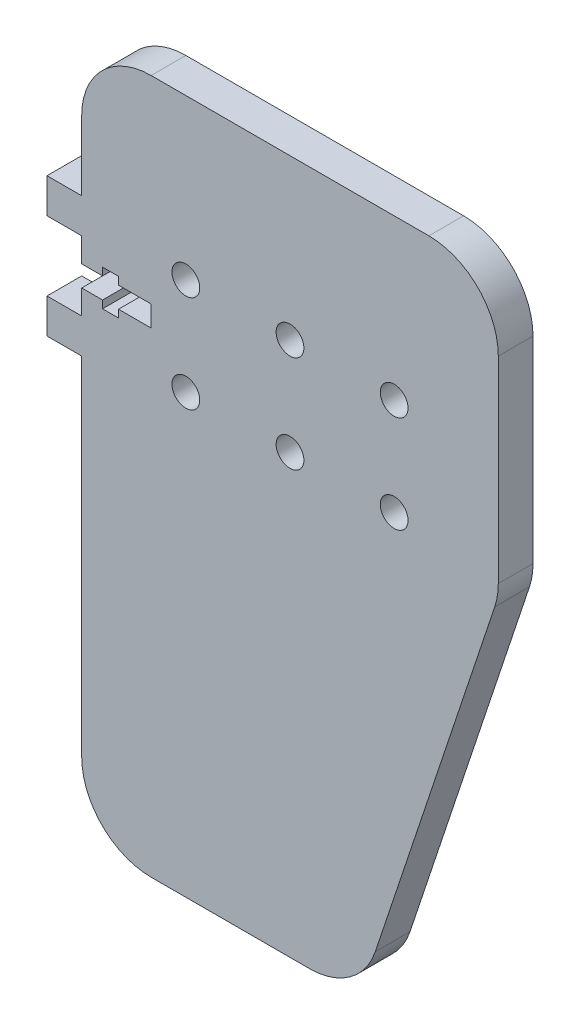
SolidWorks part; units mm, degrees
ref_plane "Plan de face" through (0, 0, 0) normal (0, 0, 1) x (1, 0, 0)
ref_plane "Plan de dessus" through (0, 0, 0) normal (0, 1, 0) x (1, 0, 0)
ref_plane "Plan de droite" through (0, 0, 0) normal (1, 0, 0) x (0, 0, -1)
sketch "Esquisse1" plane through (0, 0, 0) normal (0, 0, 1) x (1, 0, 0)
  line L0 (0, 391.1056) -> (0, -367.5965) construction
  line L1 (0, 0) -> (440.261, 0) construction
  line L2 (0, 80) -> (0, 100)
  line L3 (0, 100) -> (60, 100)
  line L4 (60, 100) -> (60, 60)
  line L5 (60, 60) -> (40, 0)
  line L6 (0, 0) -> (40, 0)
  line L8 (0, 0) -> (0, 60)
  line L9 (15, 77) -> (45, 77) construction
  circle A0 centre (15, 77) radius 2
  circle A1 centre (30, 77) radius 2
  circle A2 centre (45, 77) radius 2
  circle A3 centre (45, 63) radius 2
  circle A4 centre (30, 63) radius 2
  circle A5 centre (15, 63) radius 2
  line B0 (3, 72.6) -> (5.3, 72.6)
  line B1 (5.3, 68.5) -> (10, 68.5)
  line B2 (10, 71.5) -> (5.3, 71.5)
  line B3 (5.3, 72.6) -> (5.3, 71.5)
  line B4 (0, 70) -> (11.2208, 70) construction
  line B5 (0, 71.5) -> (0, 75)
  line B6 (-5, 75) -> (-5, 80)
  line B7 (-5, 80) -> (0, 80)
  line B8 (-5, 75) -> (0, 75)
  line B9 (0, 68.5) -> (0, 65)
  line B10 (0, 65) -> (-5, 65)
  line B11 (-5, 65) -> (-5, 60)
  line B12 (-5, 60) -> (0, 60)
  line B13 (0, 71.5) -> (0, 68.5) construction
  line B14 (0, 68.5) -> (3, 68.5)
  line B15 (5.3, 68.5) -> (5.3, 67.4)
  line B16 (3, 67.4) -> (3, 68.5)
  line B17 (10, 68.5) -> (10, 71.5)
  line B18 (3, 71.5) -> (3, 72.6)
  line B19 (5.3, 67.4) -> (3, 67.4)
  line B20 (3, 71.5) -> (0, 71.5)
  line B21 (10, 70) -> (0, 70) construction
  dimension "D10" = 4
  dimension "D2" = 20
  dimension "D3" = 40
  dimension "D4" = 40
  dimension "D5" = 100
  dimension "D6" = 60
  dimension "D7" = 15
  dimension "D8" = 15
  dimension "D9" = 15
  dimension "D11" = 7
sketch_block_instance "Insert M3 plots ep 5mm-1"
sketch_block "Insert M3 plots ep 5mm" parameters "D1"=10, "D2"=5, "D3"=5
sketch_block_instance "Decoupe Insert M3-4"
sketch_block "Decoupe Insert M3" parameters "D1"=5.2, "D2"=3, "D3"=2.3, "D4"=3, "D5"=10
extrude "Boss.-Extru.1" add sketch "Esquisse1" along normal blind 5 contours L5 L4 L3 L2 B7 B6 B8 B5 B20 B18 B0 B3 B2 B17 B1 B15 B19 B16 B14 B9 B10 B11 B12 L8 region at (27.2387, 53.1446, 0)
fillet "Congé1" radius 10 5 edges at (0, 100, 2.5) (60, 100, 2.5) (60, 60, 2.5) (0, 0, 2.5) (40, 0, 2.5)
